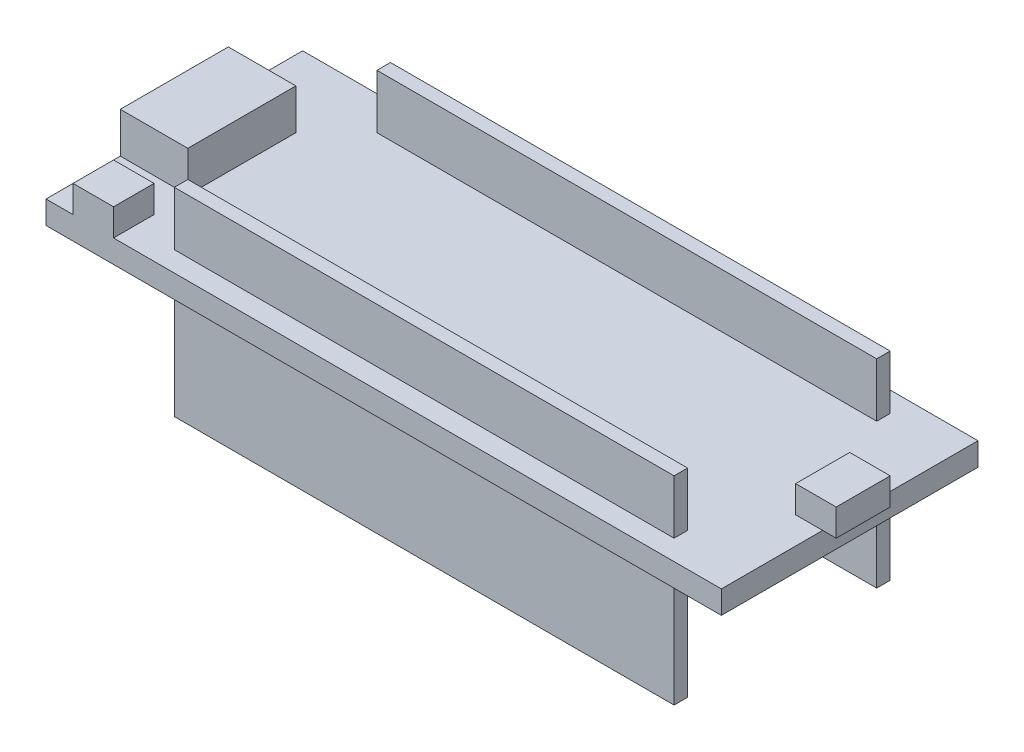
SolidWorks part; units mm, degrees
ref_plane "Спереди" through (0, 0, 0) normal (0, 0, 1) x (1, 0, 0)
ref_plane "Сверху" through (0, 0, 0) normal (0, 1, 0) x (1, 0, 0)
ref_plane "Справа" through (0, 0, 0) normal (1, 0, 0) x (0, 0, -1)
other "Центр тяжести"
sketch "Эскиз1" plane through (0, 0, 0) normal (0, 1, 0) x (1, 0, 0)
  line L1 (-25, -9.5) -> (25, -9.5)
  line L2 (-25, -9.5) -> (-25, 9.5)
  line L3 (-25, 9.5) -> (25, 9.5)
  line L4 (25, -9.5) -> (25, 9.5)
  line L5 (-25, -9.5) -> (25, 9.5) construction
  line L6 (-25, 9.5) -> (25, -9.5) construction
  point P0 (0, 0)
  dimension "D1" = 50
  dimension "D2" = 19
extrude "Бобышка-Вытянуть1" add sketch "Эскиз1" along normal blind 1.7
sketch "Эскиз2" plane through (0, 1.7, 0) normal (0, 1, 0) x (1, 0, 0)
  line L0 (-25, 9.5) -> (-25, -9.5) construction
  line L1 (-20, 4) -> (-25, 4)
  line L2 (-20, 4) -> (-20, -4)
  line L3 (-20, -4) -> (-25, -4)
  line L4 (-25, 4) -> (-25, -4)
  line L5 (-20, 4) -> (-25, -4) construction
  line L6 (-20, -4) -> (-25, 4) construction
  line L7 (33.4258, 0) -> (-35.8999, 0) construction
  point P0 (-22.5, 0)
  dimension "D1" = 5
  dimension "D2" = 8
extrude "Бобышка-Вытянуть2" add sketch "Эскиз2" along normal blind 3
sketch "Эскиз3" plane through (0, 1.7, 0) normal (0, 1, 0) x (1, 0, 0)
  line L0 (-25, -9.5) -> (25, -9.5) construction
  line L1 (-20, -9.5) -> (-23, -9.5)
  line L2 (-20, -9.5) -> (-20, -6.5)
  line L3 (-20, -6.5) -> (-23, -6.5)
  line L4 (-23, -9.5) -> (-23, -6.5)
  line L5 (-25, -4) -> (-25, -9.5) construction
  dimension "D1" = 2
  dimension "D2" = 3
  dimension "D3" = 3
extrude "Бобышка-Вытянуть3" add sketch "Эскиз3" along normal blind 2
sketch "Эскиз4" plane through (0, 1.7, 0) normal (0, 1, 0) x (1, 0, 0)
  line L6 (31.6187, 0) -> (-38.1006, 0) construction
  line L7 (20, 7) -> (-17, 7)
  line L8 (-17, 8) -> (-17, 7)
  line L9 (20, 8) -> (-17, 8)
  line L10 (20, 8) -> (20, 7)
  line L11 (25, 9.5) -> (-25, 9.5) construction
  line L12 (20, -8) -> (20, -7)
  line L13 (20, -8) -> (-17, -8)
  line L14 (-17, -8) -> (-17, -7)
  line L15 (20, -7) -> (-17, -7)
  dimension "D1" = 1
  dimension "D2" = 1.5
extrude "Бобышка-Вытянуть4" add sketch "Эскиз4" along normal blind 4 and the other way blind 10.7
sketch "Эскиз6" plane through (0, 0, 0) normal (0, -1, 0) x (1, 0, 0)
  line L0 (-25, -9.5) -> (-25, 9.5) construction
  line L1 (-22, -1) -> (-25, -1)
  line L2 (-22, -1) -> (-22, 1)
  line L3 (-22, 1) -> (-25, 1)
  line L4 (-25, -1) -> (-25, 1)
  line L5 (-22, -1) -> (-25, 1) construction
  line L6 (-22, 1) -> (-25, -1) construction
  line L7 (-29.7036, 0) -> (52.9071, 0) construction
  point P0 (-23.5, 0)
  dimension "D1" = 2
  dimension "D2" = 3
extrude "Бобышка-Вытянуть6" add sketch "Эскиз6" along normal blind 1
sketch "Эскиз7" plane through (0, 1.7, 0) normal (0, 1, 0) x (1, 0, 0)
  line L1 (26, -2) -> (23, -2)
  line L2 (26, -2) -> (26, 2)
  line L3 (26, 2) -> (23, 2)
  line L4 (23, -2) -> (23, 2)
  line L6 (23, -2) -> (26, 2) construction
  line L7 (26, -2) -> (23, 2) construction
  line L8 (-5.4773, 0) -> (45.3746, 0) construction
  point P0 (24.5, 0)
  point P7 (0, 0)
  dimension "D1" = 3
  dimension "D2" = 4
extrude "Бобышка-Вытянуть7" add sketch "Эскиз7" along normal blind 2
